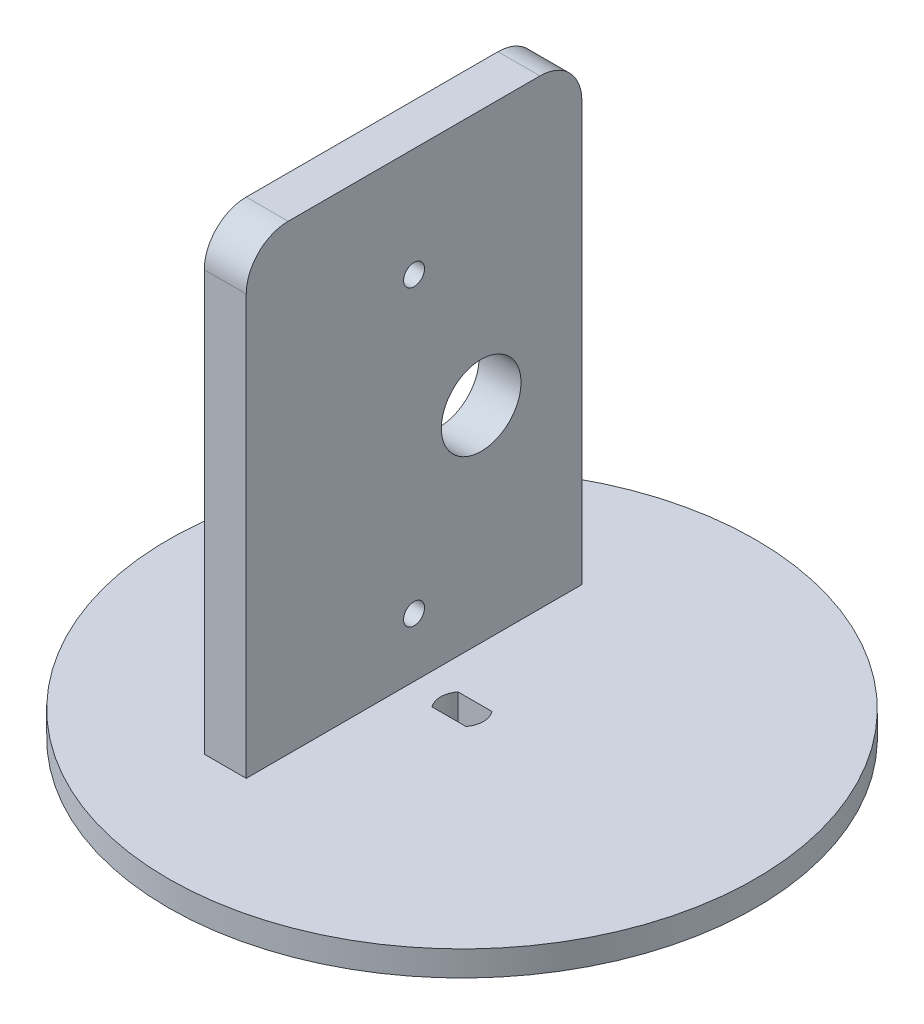
SolidWorks part; units mm, degrees
ref_plane "Alzado" through (0, 0, 0) normal (0, 0, 1) x (1, 0, 0)
ref_plane "Planta" through (0, 0, 0) normal (0, 1, 0) x (1, 0, 0)
ref_plane "Vista lateral" through (0, 0, 0) normal (1, 0, 0) x (0, 0, -1)
sketch "Croquis1" plane through (0, 0, 0) normal (0, 1, 0) x (1, 0, 0)
  line L0 (0, 0) -> (-4.7471, 0) construction
  line L1 (-2.0248, 1.55) -> (2.0248, 1.55)
  line L3 (-2.0248, -1.55) -> (2.0248, -1.55)
  circle A0 centre (0, 0) radius 35
  arc A1 (-2.0248, 1.55) -> (-2.0248, -1.55) centre (0, 0) ccw
  arc A2 (2.0248, -1.55) -> (2.0248, 1.55) centre (0, 0) ccw
  dimension "D1" = 70
  dimension "D2" = 5.1
extrude "Saliente-Extruir1" add sketch "Croquis1" along normal blind 3
sketch "Croquis2" plane through (0, 0, 0) normal (0, -1, 0) x (1, 0, 0)
  line L0 (-2.0248, 1.55) -> (2.0248, 1.55)
  line L1 (-2.0248, -1.55) -> (2.0248, -1.55)
  arc A0 (-2.0248, 1.55) -> (-2.0248, -1.55) centre (0, 0) ccw
  circle A1 centre (0, 0) radius 7.5
  arc A2 (2.0248, -1.55) -> (2.0248, 1.55) centre (0, 0) ccw
  dimension "D2" = 15
extrude "Saliente-Extruir2" add sketch "Croquis2" along normal blind 6
sketch "Croquis3" plane through (0, 0, 1.55) normal (0, 0, -1) x (-1, 0, 0)
  line L0 (-2.0248, -6) -> (2.0248, -6) construction
  circle A0 centre (0, -3) radius 1.25
  dimension "D2" = 2.5
  dimension "D1" = 3
extrude "Cortar-Extruir1" cut sketch "Croquis3" against normal blind 6
sketch "Croquis4" plane through (0, 3, 0) normal (0, 1, 0) x (1, 0, 0)
  line L1 (-5.715, 20) -> (-10.715, 20)
  line L2 (-5.715, 20) -> (-5.715, -20)
  line L3 (-5.715, -20) -> (-10.715, -20)
  line L4 (-10.715, 20) -> (-10.715, -20)
  point P4 (-5.715, 0)
  dimension "D1" = 5
  dimension "D2" = 40
extrude "Saliente-Extruir3" add sketch "Croquis4" along normal blind 55
sketch "Croquis5" plane through (-10.715, 0, 0) normal (-1, 0, 0) x (0, 0, 1)
  line L0 (-20, 3) -> (20, 3) construction
  circle A0 centre (0, 45) radius 1.25
  circle A1 centre (0, 10) radius 1.25
  circle A2 centre (-8, 27.5) radius 4.75
  dimension "D1" = 2.5
  dimension "D2" = 2.5
  dimension "D5" = 9.5
  dimension "D3" = 35
  dimension "D4" = 7
  dimension "D6" = 17.5
  dimension "D7" = 8
extrude "Cortar-Extruir2" cut sketch "Croquis5" against normal up to surface (5 mm away) up to face at (-5.715, 30.5, 0)
fillet "Redondeo1" radius 5 2 edges at (-8.215, 58, -20) (-8.215, 58, 20)
